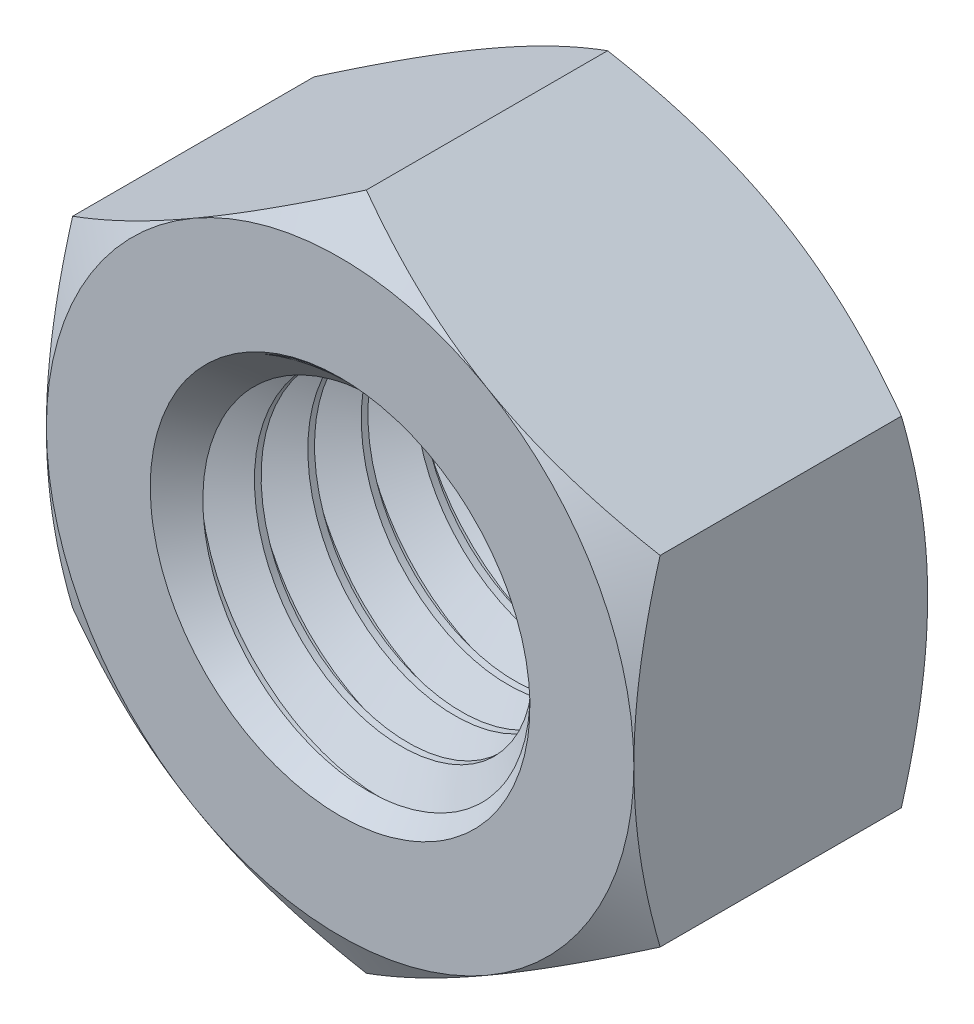
SolidWorks part; units mm, degrees
ref_plane "Front Plane" through (0, 0, 0) normal (0, 0, 1) x (1, 0, 0)
ref_plane "Top Plane" through (0, 0, 0) normal (0, 1, 0) x (1, 0, 0)
ref_plane "Right Plane" through (0, 0, 0) normal (1, 0, 0) x (0, 0, -1)
sketch "Sketch1" plane through (0, 0, 0) normal (1, 0, 0) x (0, 0, -1)
  line L0 (-2.75, 0) -> (2.75, 0) construction
  line L1 (-2.75, -5.5) -> (-2.75, 5.5) construction
  line L2 (2.75, -5.5) -> (2.75, 5.5) construction
  line L3 (-2.75, -3.5) -> (-2.75, 3.5) construction
  line L4 (-3.6875, 3.6083) -> (-3.1875, 2.7422) construction
  line L5 (-3.1875, 2.7422) -> (-2.6875, 3.6083) construction
  line L6 (-2.6875, 3.6083) -> (-3.6875, 3.6083) construction
  line L7 (-3.6563, 3.5541) -> (-2.7188, 3.5541) construction
  line L8 (-3.625, 3.5) -> (-2.75, 3.5) construction
  line L9 (-3.25, 2.8505) -> (-3.125, 2.8505) construction
  line L10 (-3.1875, 2.8505) -> (-3.1875, 2.7422) construction
  line L11 (-3.1875, 3.6083) -> (-3.1875, 3.5) construction
  point P4 (0, 0)
  point P7 (-2.75, 0)
  point P11 (2.75, 0)
  point P14 (-2.75, 0)
  point P26 (-3.1875, 3.5541)
  point P27 (-2.75, -3.5)
  dimension "Height" = 5.5
  dimension "Width" = 11
  dimension "Thread OD" = 7
  dimension "D1" = 60
  dimension "Pitch" = 1
  dimension "D2" = 0.125
sketch "Sketch2" plane through (0, 0, 0) normal (0, 0, 1) x (1, 0, 0)
  line L1 (0, 6.3509) -> (-5.5, 3.1754)
  line L2 (-5.5, 3.1754) -> (-5.5, -3.1754)
  line L3 (-5.5, -3.1754) -> (0, -6.3509)
  line L4 (0, -6.3509) -> (5.5, -3.1754)
  line L5 (5.5, -3.1754) -> (5.5, 3.1754)
  line L6 (5.5, 3.1754) -> (0, 6.3509)
  circle A0 centre (0, 0) radius 5.5 construction
  circle A1 centre (0, 0) radius 3.5
extrude "Boss-Extrude1" add sketch "Sketch2" along normal up to vertex (2.75 mm away) and the other way up to vertex (2.75 mm away) up to point (0, -5.5, 2.75) other way up to point (0, -5.5, -2.75)
sketch "Sketch3" plane through (0, 0, 2.75) normal (0, 0, 1) x (1, 0, 0)
  circle A0 centre (0, 0) radius 5.5
extrude "Cut-Extrude1" cut sketch "Sketch3" against normal through all draft 60 flip side to cut
mirror "Mirror1" about plane through (0, 0, 0) normal (0, 0, 1) of "Cut-Extrude1"
ref_axis "Center Axis 1" through (0, 0, -10.9016) along (0, 0, 1)
ref_plane "Contact Plane 1" through (0, 0, 2.75) normal (0, 0, 1) x (1, 0, 0)
ref_plane "Contact Plane 2" through (0, 0, -2.75) normal (0, 0, -1) x (-1, 0, 0)
sketch "Sketch4" plane through (0, 0, 0) normal (1, 0, 0) x (0, 0, -1)
  line L1 (-3.6563, 3.5541) -> (-3.25, 2.8505)
  line L2 (-3.25, 2.8505) -> (-3.125, 2.8505)
  line L3 (-3.125, 2.8505) -> (-2.7188, 3.5541)
  line L4 (-3.6563, 3.5541) -> (-2.7188, 3.5541) construction
  line L5 (-3.6563, 3.5541) -> (-2.7188, 3.5541)
sketch "Sketch5" plane through (0, 0, 2.75) normal (0, 0, 1) x (1, 0, 0)
  circle A0 centre (0, 0) radius 3.5 construction
  circle A1 centre (0, 0) radius 3.5
curve "Helix/Spiral1" pitch 1 height 6.5 radius 3.5 centre (0, 0, 2.75) axis (0, 0, -1) start towards (0, 1, 0)
sweep "Sweep1" add profiles "Sketch4" path "Helix/Spiral1"
sketch "Sketch6" plane through (0, 0, 2.75) normal (0, 0, 1) x (1, 0, 0)
  circle A1 centre (0, 0) radius 3.5541
extrude "Cut-Extrude2" cut sketch "Sketch6" along normal through all and the other way through all draft 45
sketch "Sketch7" plane through (0, 0, -2.75) normal (0, 0, -1) x (-1, 0, 0)
  circle A1 centre (0, 0) radius 3.5541
  circle A2 centre (0, 0) radius 3.5541
  dimension "D1" = 0
extrude "Cut-Extrude3" cut sketch "Sketch7" along normal through all and the other way through all draft 45
equation "\"D2@Sketch1\"=\"Pitch@Sketch1\"/8"
equation "\"D4@Helix/Spiral1\"=\"Pitch@Sketch1\""
equation "\"D3@Helix/Spiral1\"=\"Height@Sketch1\"+\"Pitch@Sketch1\""
